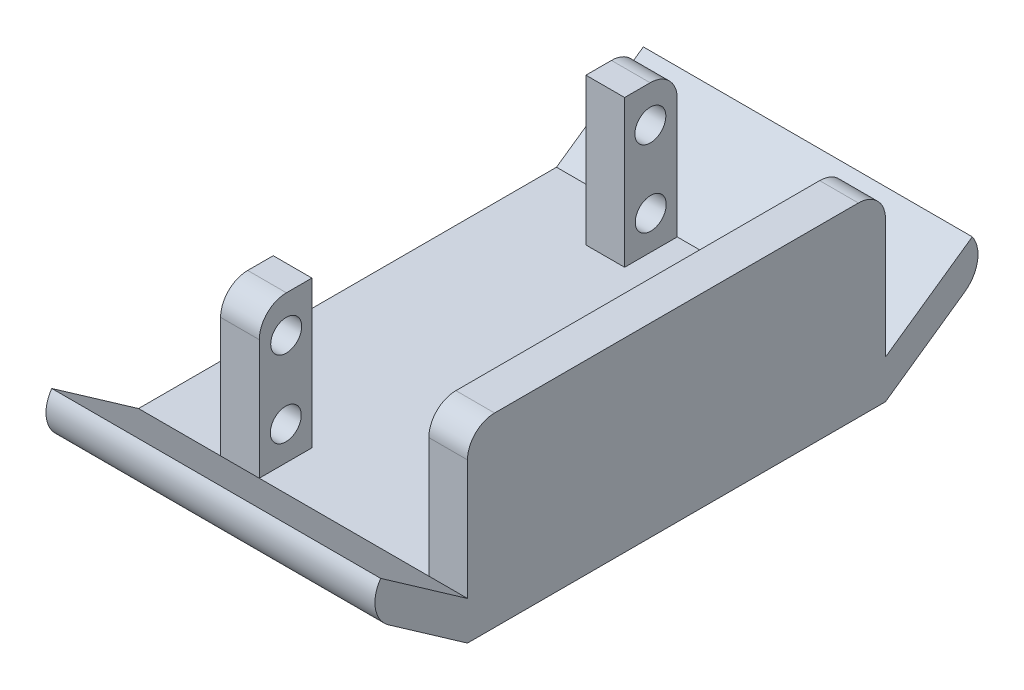
SolidWorks part; units mm, degrees
ref_plane "Front Plane" through (0, 0, 0) normal (0, 0, 1) x (1, 0, 0)
ref_plane "Top Plane" through (0, 0, 0) normal (0, 1, 0) x (1, 0, 0)
ref_plane "Right Plane" through (0, 0, 0) normal (1, 0, 0) x (0, 0, -1)
sketch "Sketch of Servo Motor" plane through (0, 0, 0) normal (0, 1, 0) x (1, 0, 0)
  line L0 (0, 0) -> (26.9, 0) construction
  line L1 (26.9, 0) -> (26.9, -40.4) construction
  line L2 (26.9, -40.4) -> (0, -40.4) construction
  line L3 (0, -40.4) -> (0, -47.2) construction
  line L4 (0, -47.2) -> (-3, -47.2) construction
  line L5 (-3, -47.2) -> (-3, -40.4) construction
  line L6 (-3, -40.4) -> (-10.6, -40.4) construction
  line L7 (-10.6, -40.4) -> (-10.6, 0) construction
  line L8 (-10.6, 0) -> (-3, 0) construction
  line L9 (-3, 0) -> (-3, 6.8) construction
  line L10 (-3, 6.8) -> (0, 6.8) construction
  line L11 (0, 6.8) -> (0, 0) construction
  line L13 (31.9, -47.2) -> (-10.6, -47.2)
  line L14 (31.9, -47.2) -> (31.9, 6.8)
  line L15 (31.9, 6.8) -> (-10.6, 6.8)
  line L16 (-10.6, -47.2) -> (-10.6, 6.8)
  dimension "D1" = 37.5
  dimension "D2" = 26.9
  dimension "D3" = 54
  dimension "D4" = 40.4
  dimension "D5" = 3
  dimension "D6" = 5
extrude "Extrude Base of Foot" add sketch "Sketch of Servo Motor" against normal blind 5
sketch "Positions of Foot Sides" plane through (0, 0, 0) normal (0, 1, 0) x (1, 0, 0)
  line L0 (-10.6, 0) -> (-3, 0) construction
  line L1 (-10.6, 6.8) -> (-10.6, -47.2) construction
  line L2 (-3, 0) -> (-3, 6.8) construction
  line L3 (31.9, 6.8) -> (-10.6, 6.8) construction
  line L4 (-3, 6.8) -> (0, 6.8) construction
  line L5 (0, 6.8) -> (0, 0) construction
  line L6 (0, 0) -> (26.9, 0) construction
  line L7 (26.9, 0) -> (26.9, -40.4) construction
  line L8 (26.9, -40.4) -> (0, -40.4) construction
  line L9 (0, -40.4) -> (0, -47.2) construction
  line L10 (-10.6, -47.2) -> (31.9, -47.2) construction
  line L11 (0, -47.2) -> (-3, -47.2) construction
  line L12 (-3, -47.2) -> (-3, -40.4) construction
  line L13 (-3, -40.4) -> (-10.6, -40.4) construction
  line L14 (-10.6, -40.4) -> (-10.6, 0) construction
  line L15 (31.9, -47.2) -> (31.9, 6.8) construction
  line L17 (31.9, 6.8) -> (26.9, 6.8)
  line L18 (31.9, 6.8) -> (31.9, -47.2)
  line L19 (31.9, -47.2) -> (26.9, -47.2)
  line L20 (26.9, 6.8) -> (26.9, -47.2)
  line L21 (0, 0) -> (5, 0)
  line L22 (0, 0) -> (0, 6.8)
  line L23 (0, 6.8) -> (5, 6.8)
  line L24 (5, 0) -> (5, 6.8)
  line L25 (0, -40.4) -> (5, -40.4)
  line L26 (0, -40.4) -> (0, -47.2)
  line L27 (0, -47.2) -> (5, -47.2)
  line L28 (5, -40.4) -> (5, -47.2)
  dimension "D1" = 3
  dimension "D2" = 5
  dimension "D3" = 5
  dimension "D4" = 26.9
extrude "Extrude Sides of Foot" add sketch "Positions of Foot Sides" along normal blind 19
fillet "Fillet Top Edges of Sides of Foot" radius 3.5 4 edges at (29.4, 19, -6.8) (2.5, 19, -6.8) (2.5, 19, 47.2) (29.4, 19, 47.2)
ref_plane "Inside RT Foot Plane" through (-10.6, 0, 0) normal (-1, 0, 0) x (0, 0, 1)
sketch "Front and Back Foot Lips" plane through (-10.6, 0, 0) normal (-1, 0, 0) x (0, 0, 1)
  line L0 (20.2, -5) -> (20.2, 19) construction
  line L1 (-6.8, -5) -> (47.2, -5) construction
  line L2 (-3.3, 19) -> (43.7, 19) construction
  line L3 (47.2, -5) -> (60.7674, 4.5) construction
  line L6 (47.2, -5) -> (47.2, 15.5) construction
  line L7 (60.7674, 4.5) -> (58.4182, 7.8551)
  line L8 (58.4182, 7.8551) -> (47.2, 0)
  line L9 (-6.8, 0) -> (47.2, 0) construction
  line L10 (47.2, 0) -> (47.2, -5)
  line L11 (47.2, -5) -> (60.7674, 4.5)
  line L12 (-6.8, 0) -> (-6.8, -5)
  line L13 (-18.0182, 7.8551) -> (-6.8, 0)
  line L14 (-20.3674, 4.5) -> (-18.0182, 7.8551)
  line L15 (-6.8, -5) -> (-20.3674, 4.5)
  dimension "D1" = 55
  dimension "D2" = 9.5
  dimension "D3" = 90
  dimension "D4" = 270
extrude "Extrude Foot Lips" add sketch "Front and Back Foot Lips" against normal through all
fillet "Fillet Foot Lips" radius 4.1 2 edges at (10.65, 4.5, 60.7674) (10.65, 4.5, -20.3674)
ref_plane "Top Servo Motor Screw Holes Plane" through (0, 0, 0) normal (-1, 0, 0) x (0, 0, 1)
sketch "Hole Dimensions for M4 Bolt" plane through (0, 0, 0) normal (-1, 0, 0) x (0, 0, 1)
  line L0 (0, 9.5) -> (49.8704, 9.5) construction
  line L2 (0, 19) -> (0, 0) construction
  line L3 (49.8704, 9.5) -> (-9.3392, 9.5) construction
  line L4 (-3.4, 0) -> (-3.3, 19) construction
  line L5 (-6.8, 0) -> (0, 0) construction
  line L6 (43.8, 0) -> (43.7, 19) construction
  line L7 (40.4, 0) -> (47.2, 0) construction
  circle A0 centre (-3.325, 14.2589) radius 2
  circle A1 centre (-3.3771, 4.3589) radius 2
  circle A2 centre (43.725, 14.2589) radius 2
  circle A3 centre (43.7771, 4.3589) radius 2
  point P23 (0, 0)
  point P24 (0, 0)
  dimension "D2" = 4
  dimension "D1" = 9.9
extrude "Extrude Cut Hole for M4 Bolt" cut sketch "Hole Dimensions for M4 Bolt" against normal blind 5
